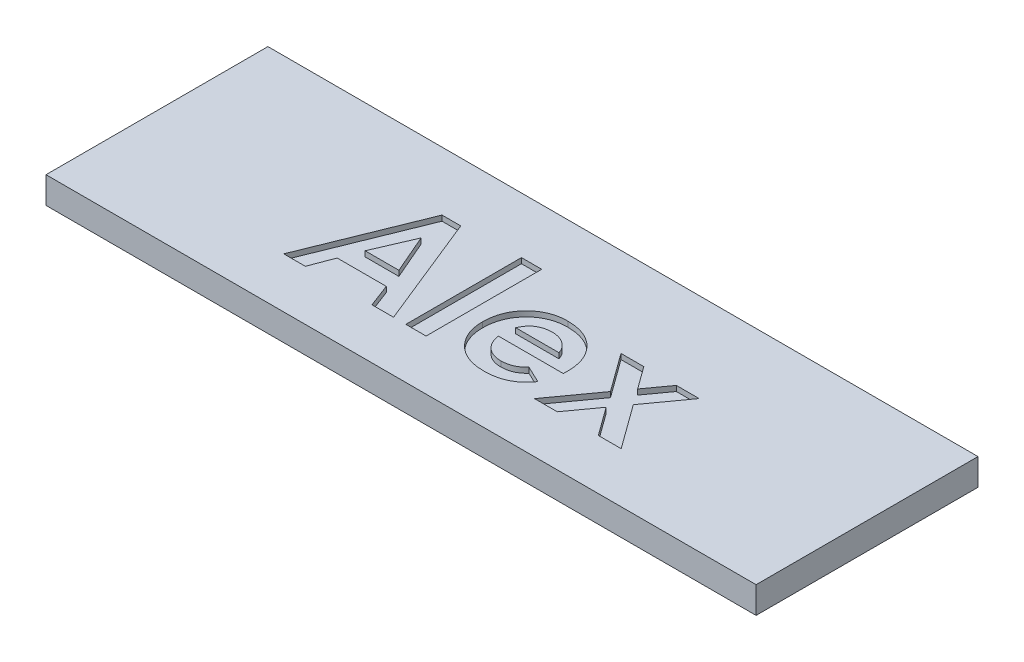
SolidWorks part; units mm, degrees
ref_plane "Front Plane" through (0, 0, 0) normal (0, 0, 1) x (1, 0, 0)
ref_plane "Top Plane" through (0, 0, 0) normal (0, 1, 0) x (1, 0, 0)
ref_plane "Right Plane" through (0, 0, 0) normal (1, 0, 0) x (0, 0, -1)
sketch "Sketch1" plane through (0, 0, 0) normal (0, 1, 0) x (1, 0, 0)
  line L0 (-18.0359, -28.097) -> (61.9641, -28.097) construction
  line L1 (-18.0359, -28.097) -> (61.9641, -28.097)
  line L2 (-18.0359, -28.097) -> (-18.0359, -3.097)
  line L3 (-18.0359, -3.097) -> (61.9641, -3.097)
  line L4 (61.9641, -28.097) -> (61.9641, -3.097)
  line L5 (-18.0359, -28.097) -> (61.9641, -3.097) construction
  line L6 (-18.0359, -3.097) -> (61.9641, -28.097) construction
  line L7 (-18.0359, -3.097) -> (-18.0359, -28.097) construction
  point P0 (21.9641, -15.597)
  point P6 (0, 0)
  point P7 (0, 0)
  point P8 (-18.0359, -28.097)
  point P13 (61.9641, -3.097)
extrude "Boss-Extrude1" add sketch "Sketch1" along normal blind 3
sketch "Sketch2" plane through (0, 0, 0) normal (0, -1, 0) x (1, 0, 0)
  circle A0 centre (-14.6216, 24.6828) radius 2.25
  circle A1 centre (-14.6216, 6.5112) radius 2.25
  circle A2 centre (54.5499, 24.6828) radius 2.25
  circle A3 centre (54.5499, 6.5112) radius 2.25
  dimension "D1" = 4.5
extrude "Cut-Extrude1" cut sketch "Sketch2" against normal blind 1.5
sketch "Sketch3" plane through (0, 3, 0) normal (0, 1, 0) x (1, 0, 0)
  line L0 (-14.1657, -22.4277) -> (58.0939, -22.4277) construction
  line L1 (-18.0359, -28.097) -> (61.9641, -28.097) construction
  text T0 "Alex" font "Century Gothic" height in points 48
  point P2 (21.9641, -28.097)
  point P3 (21.9641, -22.4277)
  point P7 (21.9641, -22.4277)
extrude "Cut-Extrude2" cut sketch "Sketch3" against normal blind 0.6
